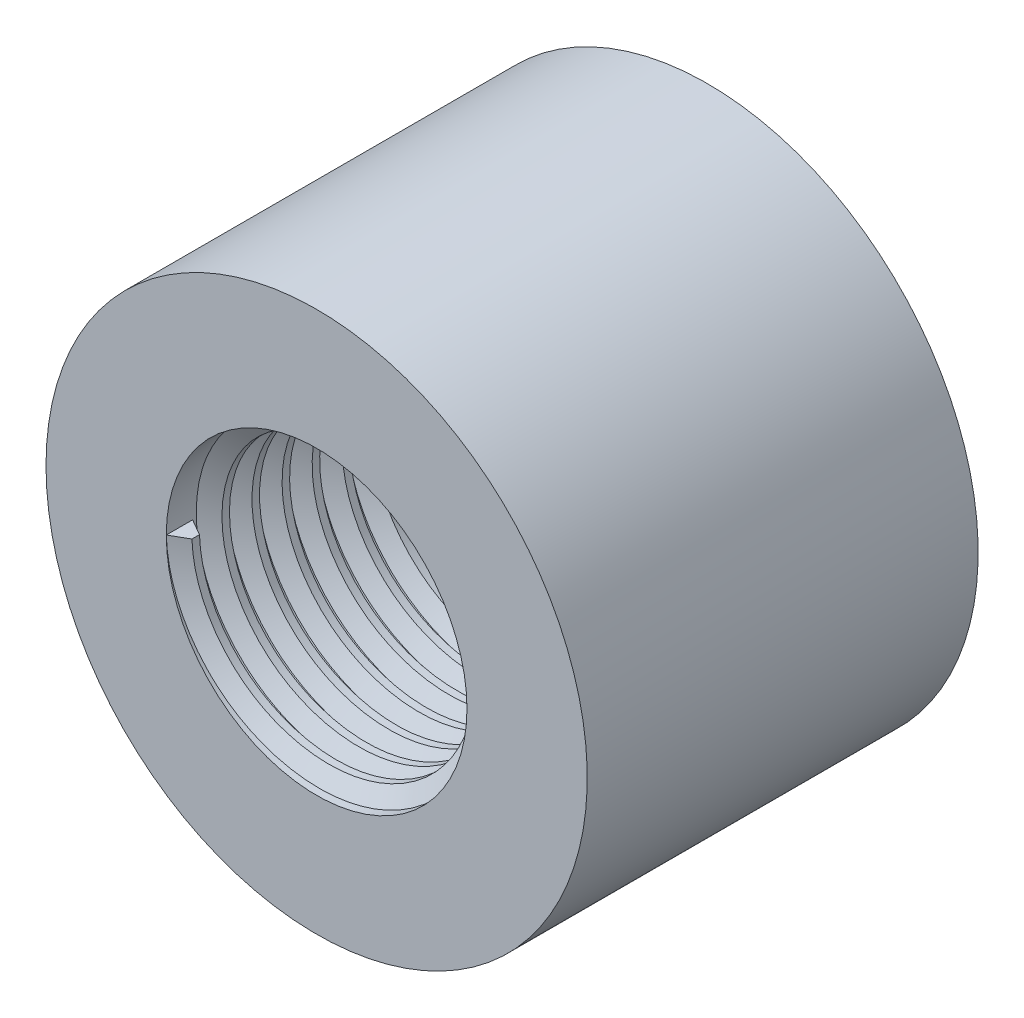
SolidWorks part; units mm, degrees
material "6061-T6 (SS)"
ref_plane "Front Plane" through (0, 0, 0) normal (0, 0, 1) x (1, 0, 0)
ref_plane "Top Plane" through (0, 0, 0) normal (0, 1, 0) x (1, 0, 0)
ref_plane "Right Plane" through (0, 0, 0) normal (1, 0, 0) x (0, 0, -1)
sketch "Sketch1" plane through (0, 0, 0) normal (0, 0, 1) x (1, 0, 0)
  circle A0 centre (0, 0) radius 9
  circle A1 centre (0, 0) radius 5
  dimension "D1" = 10
  dimension "D2" = 4
extrude "Boss-Extrude1" add sketch "Sketch1" along normal blind 13
sketch "Sketch4" plane through (0, 0, 0) normal (0, 0, -1) x (-1, 0, 0)
  circle A0 centre (0, 0) radius 7
  dimension "D1" = 14
extrude "Cut-Extrude1" cut sketch "Sketch4" against normal blind 3
thread "Thread1" start angle 0, offset 0, length 0, pitch 1, diameter 10
ref_plane "Plane2" through (-5, 0, 13) normal (0, -1, 0) x (-1, 0, 0)
sketch "Thread Profile2" plane through (-5, 0, 13) normal (0, -1, 0) x (-1, 0, 0)
  line L0 (0, 0) -> (0, 1) construction
  line L11 (0, 0) -> (0, 0.875)
  line L12 (0, 0.875) -> (-0.5413, 0.5625)
  line L13 (-0.5413, 0.5625) -> (-0.5413, 0.3125)
  line L15 (-0.5413, 0.3125) -> (0, 0)
  line L17 (-0.5413, 0.4375) -> (0, 0.4375) construction
  point P2 (0, 0)
  dimension "Pitch" = 1
  dimension "Profile_Angle" = 60
  dimension "Profile_Land" = 0.25
  dimension "Profile_Height" = 0.5413
